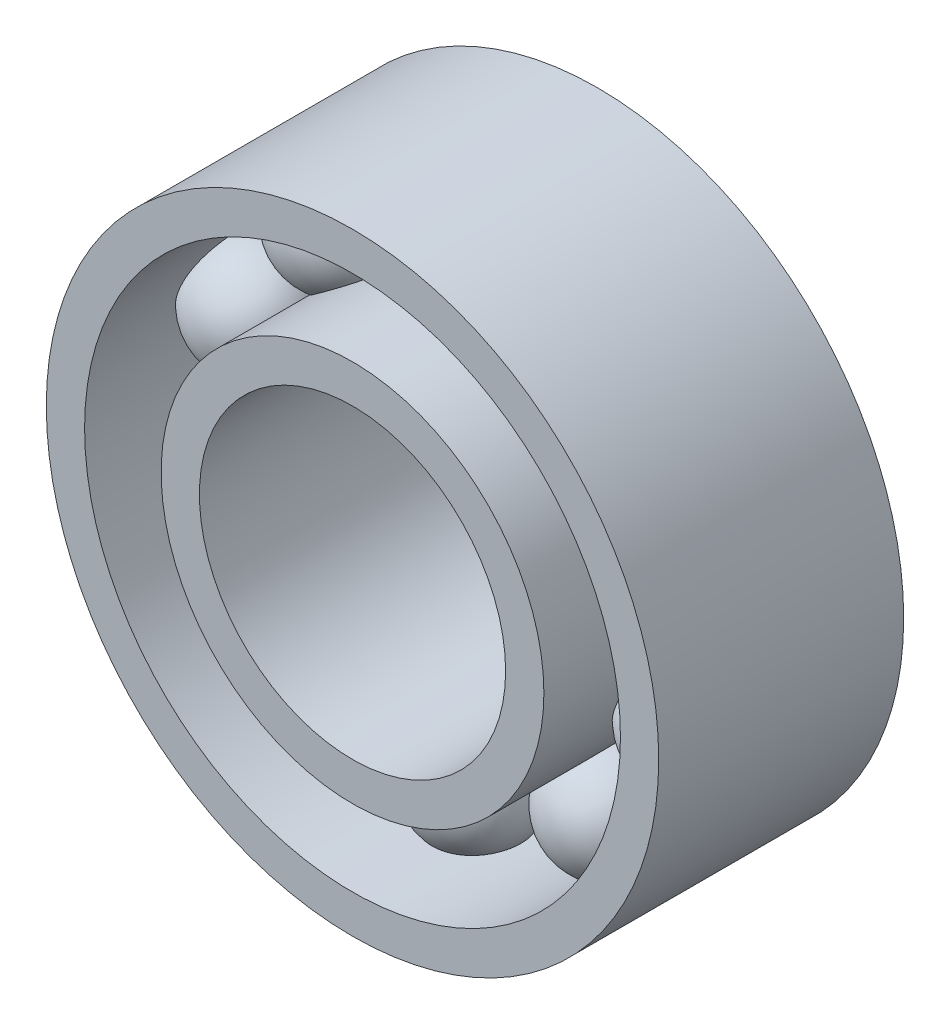
SolidWorks part; units mm, degrees
ref_plane "Front Plane" through (0, 0, 0) normal (0, 0, 1) x (1, 0, 0)
ref_plane "Top Plane" through (0, 0, 0) normal (0, 1, 0) x (1, 0, 0)
ref_plane "Right Plane" through (0, 0, 0) normal (1, 0, 0) x (0, 0, -1)
sketch "Sketch1" plane through (0, 0, 0) normal (0, 0, 1) x (1, 0, 0)
  line L0 (0, 0) -> (2.5, 0) construction
  line L1 (2.5, 0) -> (5, 0) construction
  line L2 (0, 0) -> (0, 2.5) construction
  line L3 (0, 2.5) -> (0, 3.75) construction
  line L4 (0, 3.75) -> (0, 5) construction
  circle A0 centre (0, 0) radius 5
  circle A1 centre (0, 0) radius 2.5
  circle A2 centre (0, 0) radius 3.125 construction
  circle A3 centre (0, 0) radius 4.375 construction
  circle A4 centre (0, 0) radius 3.75 construction
  point P7 (3.75, 0)
  point P13 (0, 4.375)
  point P14 (0, 3.125)
  dimension "D1" = 5
  dimension "D2" = 10
extrude "Boss-Extrude1" add sketch "Sketch1" along normal blind 4
sketch "Sketch2" plane through (0, 0, 0) normal (0, 0, 1) x (1, 0, 0)
  circle A0 centre (0, 0) radius 3.125
  circle A1 centre (0, 0) radius 4.375
  circle A2 centre (0, 0) radius 3.125 construction
  circle A3 centre (0, 0) radius 4.375 construction
extrude "Cut-Extrude1" cut sketch "Sketch2" along normal up to next
sketch "Sketch3" plane through (0, 0, 0) normal (1, 0, 0) x (0, 0, -1)
  line L1 (0, 3.75) -> (-4, 3.75) construction
  line L2 (0, 2.5) -> (0, 3.75) construction
  line L3 (-4, 5) -> (-4, -5) construction
  line L4 (-2, 4.6875) -> (-2, 2.8125)
  line L5 (-2, 2.5) -> (-2, 3.125) construction
  line L6 (0, 2.5) -> (-4, 2.5) construction
  line L7 (0, 3.125) -> (-4, 3.125) construction
  arc A0 (-2, 2.8125) -> (-2, 4.6875) centre (-2, 3.75) ccw
  point P9 (-2, 3.75)
  point P11 (-2, 3.75)
  point P18 (-2, 2.8125)
revolve "Revolve1" add sketch "Sketch3" angle 360 about L4
ref_axis "Axis1" through (0, 0, -0.2) along (0, 0, 1)
pattern_circular "CirPattern1" count 10 over 360 about axis through (0, 0, -0.2) along (0, 0, 1) of "Revolve1"
